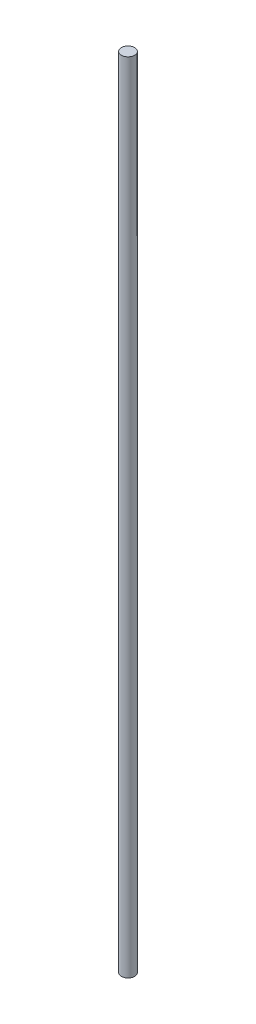
SolidWorks part; units mm, degrees
material "Pine"
ref_plane "Front" through (0, 0, 0) normal (0, 0, 1) x (1, 0, 0)
ref_plane "Top" through (0, 0, 0) normal (0, 1, 0) x (1, 0, 0)
ref_plane "Right" through (0, 0, 0) normal (1, 0, 0) x (0, 0, -1)
ref_axis "X" through (-80.9, 0, 0) along (1, 0, 0)
ref_axis "Y" through (0, -50, 0) along (0, 1, 0)
ref_axis "Z" through (0, 0, -80.9) along (0, 0, 1)
sketch "Sketch1" plane through (0, 0, 0) normal (0, 1, 0) x (1, 0, 0)
  circle A0 centre (0, 0) radius 1.5
  dimension "D1" = 3
extrude "Boss-Extrude1" add sketch "Sketch1" along normal mid plane 180
